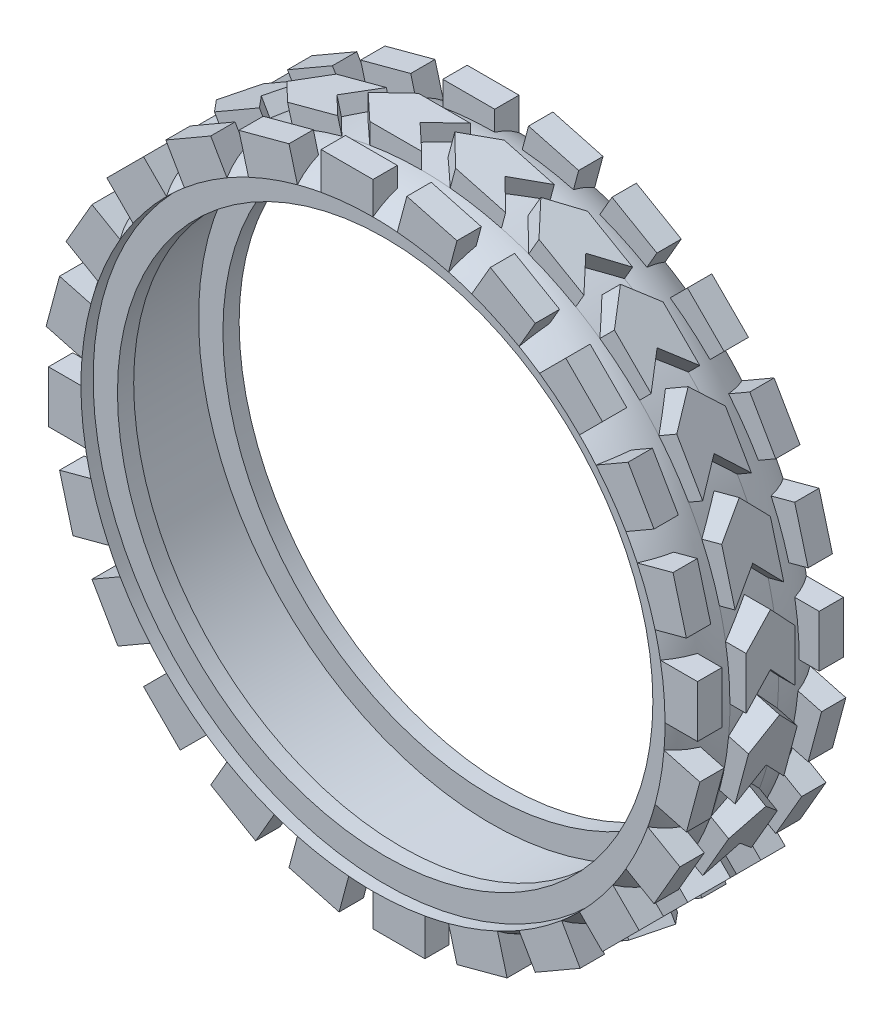
SolidWorks part; units mm, degrees
ref_plane "Front Plane" through (0, 0, 0) normal (0, 0, 1) x (1, 0, 0)
ref_plane "Top Plane" through (0, 0, 0) normal (0, 1, 0) x (1, 0, 0)
ref_plane "Right Plane" through (0, 0, 0) normal (1, 0, 0) x (0, 0, -1)
sketch "Sketch2" plane through (0, 0, 0) normal (1, 0, 0) x (0, 0, -1)
  line L0 (0, 0) -> (0, 38) construction
  line L1 (-9, 38) -> (9, 38)
  line L2 (9, 38) -> (9, 36)
  line L3 (-9, 38) -> (-9, 36)
  line L4 (9, 36) -> (7.5, 36)
  line L5 (-9, 36) -> (-7.5, 36)
  line L6 (7.5, 36) -> (7.5, 33)
  line L7 (-7.5, 36) -> (-7.5, 33)
  line L8 (7.5, 33) -> (5.5, 33)
  line L9 (-11.9819, 0) -> (11.9819, 0)
  line L10 (5.5, 33) -> (5.5, 36)
  line L11 (5.5, 36) -> (0, 36)
  line L12 (0, 36) -> (-5.5, 36)
  line L13 (-5.5, 36) -> (-5.5, 33)
  line L14 (-5.5, 33) -> (-7.5, 33)
  point P11 (0, 31)
  point P15 (0, 0)
  dimension "D1" = 38
  dimension "D2" = 18
  dimension "D3" = 2
  dimension "D4" = 1.5
  dimension "D5" = 3
  dimension "D6" = 2
  dimension "D7" = 2
revolve "Revolve2" add sketch "Sketch2" angle 360 about L9 region at (0, 36.375, 5) region at (0, 36.375, -5)
fillet "Fillet1" radius 10 2 edges at (38, 0, 9) (38, 0, -9)
ref_plane "Plane1" through (40, 0, 0) normal (1, 0, 0) x (0, 0, -1)
sketch "Sketch3" plane through (40, 0, 0) normal (1, 0, 0) x (0, 0, -1)
  line L0 (-3, 0) -> (-3, 6.394)
  line L1 (-3, -38) -> (-3, 38) construction
  line L2 (-3, 6.394) -> (0, 9.591)
  line L4 (0, 3.197) -> (-3, 0)
  line L5 (0, 3.197) -> (3, 0)
  line L7 (3, 6.394) -> (0, 9.591)
  line L8 (3, 0) -> (3, 6.394)
  line L9 (-9, 6.394) -> (-6.0009, 6.394)
  line L10 (-9, 36) -> (-9, -36) construction
  line L12 (-6.0009, 6.394) -> (-6.0009, 0)
  line L13 (-6.0009, 0) -> (-9, 0)
  line L14 (-9, 0) -> (-9, 6.394)
  line L15 (0, 55) -> (0, -55) construction
  line L16 (6.0009, 0) -> (9, 0)
  line L17 (6.0009, 6.394) -> (6.0009, 0)
  line L18 (9, 0) -> (9, 6.394)
  line L19 (9, 6.394) -> (6.0009, 6.394)
  point P18 (0, 3.197)
extrude "Boss-Extrude1" add sketch "Sketch3" against normal up to next
pattern_circular "CirPattern1" count 24 over 360 about axis through (0, 0, 0) along (0, 0, 1) of "Boss-Extrude1"
